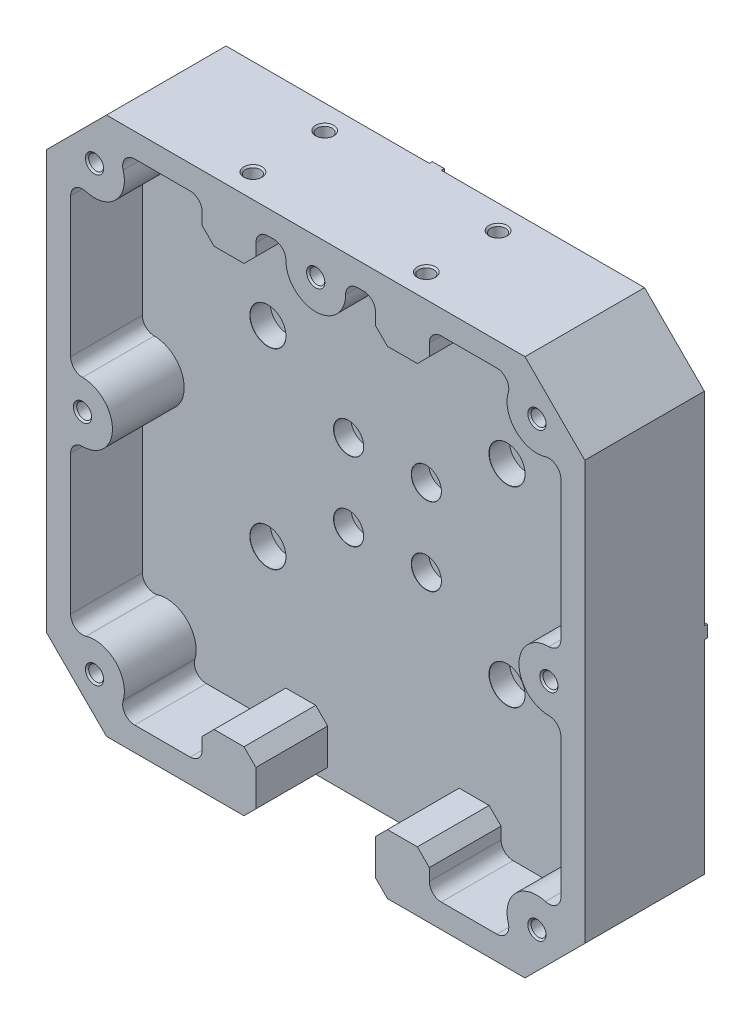
SolidWorks part; units mm, degrees
material "6061 Alloy"
ref_plane "Front Plane" through (0, 0, 0) normal (0, 0, 1) x (1, 0, 0)
ref_plane "Top Plane" through (0, 0, 0) normal (0, 1, 0) x (1, 0, 0)
ref_plane "Right Plane" through (0, 0, 0) normal (1, 0, 0) x (0, 0, -1)
sketch "Sketch1" plane through (0, 0, 0) normal (0, 0, 1) x (1, 0, 0)
  line L2 (-45, 45) -> (45, 45)
  line L3 (-45, 45) -> (-45, -45)
  line L4 (-45, -45) -> (45, -45)
  line L5 (45, 45) -> (45, -45)
  line L6 (-45, 45) -> (45, -45) construction
  line L7 (-45, -45) -> (45, 45) construction
  point P2 (0, 0)
  dimension "D2" = 90
  dimension "D3" = 90
extrude "Boss-Extrude1" add sketch "Sketch1" along normal blind 8
sketch "Z Axis Actuator Slot Position" plane through (0, 0, 8) normal (0, 0, 1) x (1, 0, 0)
  line L0 (-45, 0) -> (45, 0) construction
  line L1 (-45, 45) -> (-45, -45) construction
  line L2 (45, -45) -> (45, 45) construction
  line L3 (0, 45) -> (0, -45) construction
  line L4 (45, 45) -> (-45, 45) construction
  line L5 (-45, -45) -> (45, -45) construction
  point P0 (20, -16)
  point P3 (6.5, -6.5)
  point P17 (6.5, 6.5)
  point P18 (20, 16)
  point P19 (-20, 16)
  point P20 (-6.5, 6.5)
  point P21 (-6.5, -6.5)
  point P22 (-20, -16)
  dimension "D1" = 6.5
  dimension "D2" = 6.5
  dimension "D3" = 16
  dimension "D4" = 20
sketch "Sketch7" plane through (0, 0, 0) normal (0, 0, -1) x (-1, 0, 0)
  line L0 (-45, -45) -> (-45, 45) construction
  line L1 (45, -1) -> (-45, -1)
  line L2 (45, -1) -> (45, 1)
  line L3 (45, 1) -> (-45, 1)
  line L4 (-45, -1) -> (-45, 1)
  line L5 (45, -1) -> (-45, 1) construction
  line L6 (45, 1) -> (-45, -1) construction
  line L7 (45, 45) -> (45, -45) construction
  line L8 (0, 45) -> (0, -45) construction
  line L9 (-45, 45) -> (45, 45) construction
  line L10 (45, -45) -> (-45, -45) construction
  line L12 (1, -45) -> (-1, -45)
  line L13 (1, -45) -> (1, 45)
  line L14 (1, 45) -> (-1, 45)
  line L15 (-1, -45) -> (-1, 45)
  line L16 (1, -45) -> (-1, 45) construction
  line L17 (1, 45) -> (-1, -45) construction
  point P0 (0, 0)
  point P10 (0, 0)
  line M8 (-45, 45) -> (-45, -45)
  line M9 (-45, -45) -> (45, -45)
  line M10 (45, -45) -> (45, 45)
  line M11 (45, 45) -> (-45, 45)
  dimension "D1" = 2
  dimension "D2" = 2
extrude "Boss-Extrude2" add sketch "Sketch7" along normal blind 0.5 contours L1 L15 L3 M8 | L15 L1 L13 L3 | L15 L3 L13 M11 | L13 L1 L3 M10 | L15 L13 L1 M9
fillet "Fillet1" radius 0.5 4 edges at (1, -1, -0.25) (-1, -1, -0.25) (-1, 1, -0.25) (1, 1, -0.25)
sketch "Linear Rail Mounting Points" plane through (0, -45, 0) normal (0, -1, 0) x (-1, 0, 0)
  line L0 (-45, -8) -> (-45, 0) construction
  line L1 (-1, 0.5) -> (-1, 0) construction
  line L2 (-1, 0.5) -> (1, 0.5) construction
  point P0 (40, -11.5)
  point P1 (25, -11.5)
  point P3 (10, -11.5)
  point P5 (-5, -11.5)
  point P7 (-20, -11.5)
  point P9 (-35, -11.5)
  dimension "D1" = 10
  dimension "D2" = 11
  dimension "D3" = 26
  dimension "D4" = 41
  dimension "D5" = 4
  dimension "D6" = 19
  dimension "D7" = 12
ref_plane "Plane1" through (0, 0, 0) normal (0, -1, 0) x (-1, 0, 0)
sketch "Linear Actuator Mounting Positions" plane through (0, 0, 8) normal (0, 0, 1) x (1, 0, 0)
  line L0 (0, 45) -> (0, -45) construction
  line L1 (-45, 0) -> (45, 0) construction
  point P0 (42, -19.862)
  point P1 (42, 8.538)
  point P2 (1.5, 14.038)
  point P3 (1.5, -25.362)
  dimension "D1" = 40.5
  dimension "D2" = 5.5
  dimension "D3" = 28.4
  dimension "D4" = 5.5
  dimension "D5" = 1.5
  dimension "D6" = 25.362
sketch "Support Vertical Mounting Points" plane through (0, 0, 8) normal (0, 0, 1) x (1, 0, 0)
  line L0 (45, -45) -> (45, 45) construction
  line L3 (45, 45) -> (-45, 45) construction
  point P0 (40, 35)
  point P1 (10, 40)
  dimension "D1" = 5
  dimension "D2" = 10
  dimension "D3" = 30
  dimension "D4" = 5
sketch "Support Horizontal Mounting Points" plane through (45, 0, 0) normal (1, 0, 0) x (0, 0, -1)
  line L0 (-8, -45) -> (0, -45) construction
  line L1 (-8, -45) -> (-8, 45) construction
  line L2 (-8, 45) -> (0, 45) construction
  line L3 (0, 1) -> (0, 45) construction
  line L4 (0, -45) -> (0, -1) construction
  line L5 (-8, 0) -> (0.5, 0) construction
  line L6 (0.5, 1) -> (0.5, -1) construction
  point P0 (-3, -40)
  point P1 (-3, 40)
  point P6 (-5, -40)
  point P7 (-5, 40)
  point P14 (-5, 0)
  point P17 (-3, 0)
  dimension "D1" = 5
  dimension "D2" = 5
  dimension "D3" = 5
  dimension "D4" = 5
  dimension "D5" = 5
  dimension "D6" = 5
sketch "Sketch26" plane through (0, 0, 8) normal (0, 0, 1) x (1, 0, 0)
  line L0 (-45, 16) -> (-17, 0)
  line L1 (-17, 0) -> (-45, -16)
  line L3 (-45, -16) -> (-45, 16)
  line L4 (-45, 0) -> (45, 0) construction
  line L6 (-45, 45) -> (-45, -45) construction
  line L7 (45, -45) -> (45, 45) construction
  dimension "D1" = 28
  dimension "D2" = 32
extrude "Cut-Extrude1" [suppressed] cut sketch "Sketch26" against normal through all
fillet "Fillet2" [suppressed] radius 3
chamfer "Chamfer1" [suppressed] distance 1 angle 45
sketch "Sketch27" plane through (0, 0, 8) normal (0, 0, 1) x (1, 0, 0)
  line L4 (-40, 40) -> (-40, -40)
  line L6 (-40, 40) -> (-40, -40)
  line L7 (-40, -40) -> (40, -40)
  line L11 (-40, -40) -> (40, -40)
  line L13 (40, 40) -> (-40, 40)
  line L15 (40, 40) -> (-40, 40)
  line L16 (40, -40) -> (40, 40)
  line L23 (40, -40) -> (40, 40)
  circle A22 centre (-20, 16) radius 7.5
  circle A23 centre (-6.5, 6.5) radius 5
  circle A24 centre (1.5, 14.038) radius 4
  circle A25 centre (10, 40) radius 4
  circle A26 centre (6.5, 6.5) radius 5
  circle A27 centre (6.5, -6.5) radius 5
  circle A28 centre (-6.5, -6.5) radius 5
  circle A29 centre (-20, -16) radius 7.5
  circle A30 centre (20, -16) radius 7.5
  circle A31 centre (20, 16) radius 7.5
  circle A32 centre (1.5, -25.362) radius 4
  circle A33 centre (42, -19.862) radius 4
  circle A34 centre (42, 8.538) radius 4
  circle A35 centre (40, 35) radius 4
  dimension "D1" = 15
  dimension "D2" = 10
  dimension "D3" = 8
  dimension "D4" = 5
extrude "Cut-Extrude2" [suppressed] cut sketch "Sketch27" against normal blind 4.5
sketch "Sketch28" [suppressed] plane through (0, 0, 13.5) normal (0, 0, 1) x (1, 0, 0)
  line L0 (51.6428, -22.1747) -> (58.7052, -33.0775)
  line L1 (49.5685, -28.396) -> (55.3356, -35.2925)
  line L2 (44.0331, -27.8133) -> (35.4164, -34.5641)
  line L3 (33.5, -38.5) -> (33.5, -51.5)
  line L4 (38.5, -56.5) -> (51.5, -56.5)
  line L5 (56.5, -38.5) -> (56.5, -51.5)
  line L6 (72.5, -29) -> (72.5, -20)
  line L7 (18.5048, -25.25) -> (21.5359, -20)
  line L8 (85, -70) -> (85, -68.3261)
  line L11 (85, -32.9979) -> (85, -29)
  line L12 (85, -61.3979) -> (85, -39.9261)
  line L13 (85, -61.3979) -> (85, -39.9261)
  line L18 (85, -32.9979) -> (85, -29)
  line L22 (32.5, -29) -> (32.5, -20)
  line L23 (17.5048, -64.75) -> (20.5359, -70)
  line L24 (27.4641, -70) -> (30.4952, -64.75)
  line L25 (83.2679, -20) -> (81.5359, -23)
  line L27 (58.5048, -64.75) -> (61.5359, -70)
  line L28 (71.4952, -64.75) -> (68.4641, -70)
  line L29 (83.1363, -65.8973) -> (84.2356, -70)
  line L31 (85, -70) -> (85, -68.3261)
  line L39 (26.4186, -52.8142) -> (25.2131, -53.503)
  line L42 (85, -68.3261) -> (85, -70)
  line L57 (85, -70) -> (84.2356, -70)
  line L65 (26.4186, -52.8142) -> (25.2131, -53.503)
  line L66 (18.4329, -57.3774) -> (6, -64.4819)
  line L67 (18.4329, -57.3774) -> (6, -64.4819)
  line L68 (6, -64.4819) -> (6, -70)
  line L69 (6, -70) -> (42.5164, -70)
  line L73 (6, -70) -> (42.5164, -70)
  line L75 (50.4836, -70) -> (85, -70)
  line L77 (6, -64.4819) -> (6, -70)
  line L78 (50.4836, -70) -> (85, -70)
  line L79 (85, -21) -> (85, -20)
  line L80 (85, -21) -> (85, -20)
  line L81 (85, -20) -> (59, -20)
  line L82 (85, -20) -> (59, -20)
  line L83 (51, -20) -> (6, -20)
  line L84 (51, -20) -> (6, -20)
  line L85 (6, -20) -> (6, -25.5181)
  line L86 (6, -20) -> (6, -25.5181)
  line L87 (6, -25.5181) -> (18.4329, -32.6226)
  line L88 (6, -25.5181) -> (18.4329, -32.6226)
  line L89 (25.2131, -36.497) -> (26.4186, -37.1858)
  line L90 (25.2131, -36.497) -> (26.4186, -37.1858)
  circle A0 centre (55, -20) radius 4 construction
  circle A1 centre (65, -29) radius 7.5 construction
  circle A2 centre (46.5, -30.962) radius 4 construction
  circle A3 centre (51.5, -38.5) radius 5 construction
  circle A4 centre (38.5, -38.5) radius 5 construction
  circle A5 centre (38.5, -38.5) radius 5 construction
  circle A6 centre (38.5, -51.5) radius 5 construction
  circle A7 centre (38.5, -51.5) radius 5 construction
  circle A8 centre (51.5, -51.5) radius 5 construction
  circle A9 centre (51.5, -38.5) radius 5 construction
  arc A10 (85, -61.3979) -> (85, -68.3261) centre (87, -64.862) ccw
  arc A11 (85, -61.3979) -> (85, -68.3261) centre (87, -64.862) ccw
  arc A12 (50.4836, -70) -> (42.5164, -70) centre (46.5, -70.362) ccw
  arc A13 (85, -32.9979) -> (85, -39.9261) centre (87, -36.462) ccw
  arc A14 (85, -32.9979) -> (85, -39.9261) centre (87, -36.462) ccw
  circle A17 centre (65, -29) radius 7.5 construction
  arc A20 (50.4836, -70) -> (42.5164, -70) centre (46.5, -70.362) ccw
  circle A26 centre (51.5, -51.5) radius 5 construction
  circle A27 centre (46.5, -30.962) radius 4 construction
  circle A28 centre (65, -29) radius 7.5 construction
  circle A29 centre (65, -61) radius 7.5 construction
  circle A30 centre (65, -61) radius 7.5 construction
  arc A38 (85, -21) -> (85, -29) centre (85, -25) ccw
  arc A39 (85, -21) -> (85, -29) centre (85, -25) ccw
  arc A40 (51, -20) -> (59, -20) centre (55, -20) ccw
  arc A41 (51, -20) -> (59, -20) centre (55, -20) ccw
  arc A45 (26.4186, -52.8142) -> (26.4186, -37.1858) centre (21.9533, -45) ccw
  arc A46 (26.4186, -52.8142) -> (26.4186, -37.1858) centre (21.9533, -45) ccw
  arc A47 (18.4329, -57.3774) -> (25.2131, -53.503) centre (25, -61) ccw
  arc A48 (18.4329, -57.3774) -> (25.2131, -53.503) centre (25, -61) ccw
  arc A49 (25.2131, -36.497) -> (18.4329, -32.6226) centre (25, -29) ccw
  arc A50 (25.2131, -36.497) -> (18.4329, -32.6226) centre (25, -29) ccw
  dimension "D2" = 75
  dimension "D3" = 60
  dimension "D4" = 60
  dimension "D5" = 60
  dimension "D6" = 60
  dimension "D7" = 60
  dimension "D8" = 60
  dimension "D1" = 0
extrude "Boss-Extrude3" [suppressed] add sketch "Sketch28" along normal up to surface (4.5 mm away)
sketch "Sketch29" plane through (45, 0, 0) normal (1, 0, 0) x (0, 0, -1)
  line L1 (-5.5, -42.5) -> (-0.5, -42.5)
  line L2 (-5.5, -42.5) -> (-5.5, -37.5)
  line L3 (-5.5, -37.5) -> (-0.5, -37.5)
  line L4 (-0.5, -42.5) -> (-0.5, -37.5)
  line L5 (-5.5, -42.5) -> (-0.5, -37.5) construction
  line L6 (-5.5, -37.5) -> (-0.5, -42.5) construction
  line L7 (-5.5, -2.5) -> (-0.5, -2.5)
  line L8 (-5.5, -2.5) -> (-5.5, 2.5)
  line L9 (-5.5, 2.5) -> (-0.5, 2.5)
  line L10 (-0.5, -2.5) -> (-0.5, 2.5)
  line L11 (-5.5, -2.5) -> (-0.5, 2.5) construction
  line L12 (-5.5, 2.5) -> (-0.5, -2.5) construction
  line L13 (-5.5, 37.5) -> (-0.5, 37.5)
  line L14 (-5.5, 37.5) -> (-5.5, 42.5)
  line L15 (-5.5, 42.5) -> (-0.5, 42.5)
  line L16 (-0.5, 37.5) -> (-0.5, 42.5)
  line L17 (-5.5, 37.5) -> (-0.5, 42.5) construction
  line L18 (-5.5, 42.5) -> (-0.5, 37.5) construction
  point P0 (-3, -40)
  point P6 (-3, 0)
  point P12 (-3, 40)
  dimension "D1" = 5
extrude "Boss-Extrude4" [suppressed] add sketch "Sketch29" against normal blind 21
fillet "Fillet3" [suppressed] radius 2
fillet "Fillet4" [suppressed] radius 1
sketch "Sketch30" plane through (45, 0, 0) normal (1, 0, 0) x (0, 0, -1)
  line L8 (-3, -42) -> (-3, 42)
  line L10 (-3, -42) -> (-3, 42)
  line L20 (-5, 42) -> (-5, -42)
  line L21 (-5, -42) -> (-3, -42)
  line L23 (-3, 42) -> (-5, 42)
  line L24 (-5, 42) -> (-5, -42)
  line L25 (-5, -42) -> (-3, -42)
  line L27 (-3, 42) -> (-5, 42)
  circle A0 centre (-13, -20) radius 5
  circle A1 centre (-5, -20) radius 5
  circle A2 centre (-13, -45) radius 5
  circle A3 centre (-5, -45) radius 5
  circle A4 centre (-13, -70) radius 5
  circle A5 centre (-5, -70) radius 5
  dimension "D1" = 10
  dimension "D2" = 3
extrude "Cut-Extrude3" [suppressed] cut sketch "Sketch30" against normal blind 3
sketch "Sketch31" [suppressed] plane through (0, 0, 18) normal (0, 0, 1) x (1, 0, 0)
  line L0 (87, -64.862) -> (90, -64.862) construction
  line L1 (90, -75) -> (90, -15) construction
  line L2 (90, -68.862) -> (87, -68.862)
  line L3 (90, -68.862) -> (90, -60.862)
  line L4 (90, -60.862) -> (87, -60.862)
  line L5 (87, -68.862) -> (87, -60.862)
  line L8 (90, -32.462) -> (87, -32.462)
  line L9 (90, -32.462) -> (90, -40.462)
  line L10 (90, -40.462) -> (87, -40.462)
  line L11 (87, -32.462) -> (87, -40.462)
  line L12 (87, -36.462) -> (90, -36.462) construction
  line L13 (87, -40.4174) -> (87, -24.5826) construction
  dimension "D1" = 8
extrude "Boss-Extrude5" [suppressed] add sketch "Sketch31" against normal up to surface (15 mm away)
fillet "Fillet5" [suppressed] radius 2
sketch "Sketch32" [suppressed] plane through (87, 0, 0) normal (1, 0, 0) x (0, 0, -1)
  line L1 (-7.0993, -40.462) -> (-10.9007, -40.462)
  line L9 (-7.0993, -40.462) -> (-10.9007, -40.462)
  arc A2 (-9, -42) -> (-10.9007, -40.462) centre (-13, -45) ccw
  arc A3 (-7.0993, -40.462) -> (-9, -42) centre (-5, -45) ccw
  arc A4 (-9, -42) -> (-10.9007, -40.462) centre (-13, -45) ccw
  arc A5 (-7.0993, -40.462) -> (-9, -42) centre (-5, -45) ccw
  dimension "D1" = 0
extrude "Boss-Extrude6" [suppressed] add sketch "Sketch32" along normal up to surface (3 mm away)
hole_wizard "Tap Drill for M2 Tap1" [suppressed] positions "Sketch11" profile "Sketch12" hole size "M2" standard "GB"
sketch "Sketch11" plane through (0, -75, 0) normal (0, -1, 0) x (-1, 0, 0)
  line L0 (0, 0) -> (-44, 0) construction
  line L1 (0, -18) -> (0, 0) construction
  point P0 (-80, -9.5)
  point P3 (-65, -9.5)
  point P6 (-50, -9.5)
  point P9 (-35, -9.5)
  point P12 (-20, -9.5)
  point P15 (-5, -9.5)
  dimension "D1" = 9.5
  dimension "D2" = 5
  dimension "D3" = 20
  dimension "D4" = 35
  dimension "D5" = 50
  dimension "D6" = 65
  dimension "D7" = 80
sketch "Sketch12" plane through (80, -75, 9.5) normal (1, 0, 0) x (0, 0, -1)
  line L0 (0, 0) -> (0, 10.4807)
  line L1 (0, 10.4807) -> (0.8, 10)
  line L2 (0.8, 10) -> (0.8, 0.025)
  line L3 (0.8, 0.025) -> (0.825, 0)
  line L5 (0.825, 0) -> (0, 0)
  line L6 (-0.8, 0.025) -> (-0.825, 0) construction
  line L10 (0, 10.4807) -> (-0.8, 10) construction
  line L11 (0, -6.35) -> (0, 107.95) construction
  dimension "Hole Dia." = 1.6
  dimension "Hole Depth" = 10
  dimension "Near C'Sink Dia." = 1.65
  dimension "Near C'Sink Angle" = 90
  dimension "Drill Angle" = 118
mirror "Mirror1" [suppressed] about plane through (0, 0, 0) normal (0, -1, 0)
hole_wizard "CBORE for M2.5 Hexagon socket head cap screws1" positions "Sketch8" profile "Sketch9" counterbore size "M2.5" standard "GB" end condition through all
sketch "Sketch8" plane through (0, 0, 8) normal (0, 0, 1) x (1, 0, 0)
  point P0 (-6.5, 6.5)
  point P3 (6.5, 6.5)
  point P6 (-6.5, -6.5)
  point P9 (6.5, -6.5)
sketch "Sketch9" plane through (-6.5, 6.5, 8) normal (1, 0, 0) x (0, -1, 0)
  line L0 (0, 0) -> (0, 8.5)
  line L1 (0, 8.5) -> (1.35, 8.5)
  line L3 (1.35, 8.5) -> (1.35, 2.9)
  line L4 (2.5, 2.9) -> (1.35, 2.9)
  line L5 (2.5, 2.9) -> (2.5, 0.025)
  line L6 (2.5, 0.025) -> (2.525, 0)
  line L7 (2.525, 0) -> (0, 0)
  line L8 (-2.5, 0.025) -> (-2.525, 0) construction
  line L11 (0, -6.35) -> (0, 107.95) construction
  dimension "Thru Hole Dia." = 2.7
  dimension "Thru Hole Depth" = 8.5
  dimension "C'Bore Dia." = 5
  dimension "C'Bore Depth" = 2.9
  dimension "Near C'Sink Dia." = 5.05
  dimension "Near C'Sink Angle" = 90
hole_wizard "CBORE for M3 Hexagon socket head cap screws1" positions "Sketch4" profile "Sketch6" counterbore size "M3" standard "GB" end condition through all
sketch "Sketch4" plane through (0, 0, 8) normal (0, 0, 1) x (1, 0, 0)
  point P0 (20, -16)
  point P4 (20, 16)
  point P7 (-20, 16)
  point P10 (-20, -16)
sketch "Sketch6" plane through (20, -16, 8) normal (1, 0, 0) x (0, -1, 0)
  line L0 (0, 0) -> (0, 8.5)
  line L1 (0, 8.5) -> (1.6, 8.5)
  line L3 (1.6, 8.5) -> (1.6, 3.4)
  line L4 (3, 3.4) -> (1.6, 3.4)
  line L5 (3, 3.4) -> (3, 0.025)
  line L6 (3, 0.025) -> (3.025, 0)
  line L7 (3.025, 0) -> (0, 0)
  line L8 (-3, 0.025) -> (-3.025, 0) construction
  line L11 (0, -6.35) -> (0, 107.95) construction
  dimension "Thru Hole Dia." = 3.2
  dimension "Thru Hole Depth" = 8.5
  dimension "C'Bore Dia." = 6
  dimension "C'Bore Depth" = 3.4
  dimension "Near C'Sink Dia." = 6.05
  dimension "Near C'Sink Angle" = 90
other "Graphic1"
other "Graphic (Closed) -1"
other "Graphic (Closed) -2"
chamfer "Chamfer2" distance 10 angle 45 4 edges at (-45, 45, 4) (-45, -45, 4) (45, 45, 4) (45, -45, 4)
sketch "Sketch34" plane through (0, 0, 8) normal (0, 0, 1) x (1, 0, 0)
  line L8 (35, 45) -> (-35, 45)
  line L9 (-35, 45) -> (-45, 35)
  line L10 (-45, 35) -> (-45, -35)
  line L11 (-45, -35) -> (-35, -45)
  line L12 (-35, -45) -> (35, -45)
  line L13 (35, -45) -> (45, -35)
  line L14 (45, -35) -> (45, 35)
  line L15 (45, 35) -> (35, 45)
  line L16 (35, 45) -> (-35, 45)
  line L17 (-35, 45) -> (-45, 35)
  line L18 (-45, 35) -> (-45, -35)
  line L19 (-45, -35) -> (-35, -45)
  line L20 (-35, -45) -> (35, -45)
  line L21 (35, -45) -> (45, -35)
  line L22 (45, -35) -> (45, 35)
  line L23 (45, 35) -> (35, 45)
  line L32 (33.3431, 41) -> (-33.3431, 41)
  line L33 (-33.3431, 41) -> (-41, 33.3431)
  line L34 (-41, 33.3431) -> (-41, -33.3431)
  line L35 (-41, -33.3431) -> (-33.3431, -41)
  line L36 (-33.3431, -41) -> (33.3431, -41)
  line L37 (33.3431, -41) -> (41, -33.3431)
  line L38 (41, -33.3431) -> (41, 33.3431)
  line L39 (41, 33.3431) -> (33.3431, 41)
  line L40 (33.3431, 41) -> (-33.3431, 41)
  line L41 (-33.3431, 41) -> (-41, 33.3431)
  line L42 (-41, 33.3431) -> (-41, -33.3431)
  line L43 (-41, -33.3431) -> (-33.3431, -41)
  line L44 (-33.3431, -41) -> (33.3431, -41)
  line L45 (33.3431, -41) -> (41, -33.3431)
  line L46 (41, -33.3431) -> (41, 33.3431)
  line L47 (41, 33.3431) -> (33.3431, 41)
  dimension "D1" = 0
  dimension "D2" = 4
extrude "Boss-Extrude8" add sketch "Sketch34" along normal blind 12
sketch "Sketch35" plane through (0, 0, 20) normal (0, 0, 1) x (1, 0, 0)
  line L1 (35, 45) -> (-35, 45) construction
  line L2 (-45, 35) -> (-45, -35) construction
  line L3 (0, 45) -> (0, -45) construction
  line L4 (0, 45) -> (0, -45) construction
  line L5 (-45, 0) -> (45, 0) construction
  point P0 (-37, 37)
  point P3 (37, 37)
  point P8 (0, 39)
  point P12 (37, -37)
  point P17 (-37, -37)
  point P18 (-39, 0)
  point P19 (39, 0)
  dimension "D1" = 8
  dimension "D2" = 8
  dimension "D3" = 6
  dimension "D4" = 6
sketch "Sketch36" plane through (0, 0, 8) normal (0, 0, 1) x (1, 0, 0)
  line L8 (45, 35) -> (35, 45)
  line L9 (35, 45) -> (-35, 45)
  line L10 (-35, 45) -> (-45, 35)
  line L11 (-45, 35) -> (-45, -35)
  line L12 (-45, -35) -> (-35, -45)
  line L13 (-35, -45) -> (35, -45)
  line L14 (35, -45) -> (45, -35)
  line L15 (45, -35) -> (45, 35)
  line L16 (45, 35) -> (35, 45)
  line L17 (35, 45) -> (-35, 45)
  line L18 (-35, 45) -> (-45, 35)
  line L19 (-45, 35) -> (-45, -35)
  line L20 (-45, -35) -> (-35, -45)
  line L21 (-35, -45) -> (35, -45)
  line L22 (35, -45) -> (45, -35)
  line L23 (45, -35) -> (45, 35)
  circle A0 centre (-37, 37) radius 5
  circle A1 centre (0, 39) radius 5
  circle A2 centre (37, 37) radius 5
  circle A3 centre (39, 0) radius 5
  circle A4 centre (-39, 0) radius 5
  circle A5 centre (-37, -37) radius 5
  circle A6 centre (37, -37) radius 5
  line M9 (41, 33.3431) -> (33.3431, 41)
  line M10 (33.3431, 41) -> (-33.3431, 41)
  line M11 (-33.3431, 41) -> (-41, 33.3431)
  line M12 (-41, 33.3431) -> (-41, -33.3431)
  line M13 (-41, -33.3431) -> (-33.3431, -41)
  line M15 (33.3431, -41) -> (41, -33.3431)
  line M16 (41, -33.3431) -> (41, 33.3431)
  dimension "D1" = 10
  dimension "D2" = 0
extrude "Boss-Extrude9" add sketch "Sketch36" along normal up to surface (12 mm away) contours A0 M11 | A1 M10 | A2 M9 | A3 M16 | A4 M12 | A5 M13 | A6 M15 up to face at (0, 0, 20)
sketch "Sketch37" plane through (0, 0, 20) normal (0, 0, 1) x (1, 0, 0)
  line L0 (-33.3431, -41) -> (33.3431, -41) construction
  line L1 (10, -45) -> (-10, -45)
  line L2 (10, -45) -> (10, -37)
  line L3 (10, -37) -> (-10, -37)
  line L4 (-10, -45) -> (-10, -37)
  line L5 (10, -45) -> (-10, -37) construction
  line L6 (10, -37) -> (-10, -45) construction
  line L7 (-35, -45) -> (35, -45) construction
  point P0 (0, -41)
  dimension "D1" = 20
extrude "Cut-Extrude4" cut sketch "Sketch37" against normal up to surface (12 mm away) up to face at (0, 3.4091, 8)
sketch "Sketch41" plane through (0, 0, 8) normal (0, 0, 1) x (1, 0, 0)
  line L1 (-19, 41) -> (-10, 41)
  line L2 (-19, 41) -> (-19, 35)
  line L3 (-19, 35) -> (-10, 35)
  line L4 (-10, 41) -> (-10, 35)
  line L5 (0, 45) -> (0, -45) construction
  line L6 (35, 45) -> (-35, 45) construction
  line L7 (10, -45) -> (-10, -45) construction
  line L8 (-45, 0) -> (45, 0) construction
  line L9 (-45, 35) -> (-45, -35) construction
  line L10 (45, -35) -> (45, 35) construction
  line L11 (-10, -41) -> (-10, -35)
  line L12 (-19, -35) -> (-10, -35)
  line L13 (-19, -41) -> (-19, -35)
  line L14 (-19, -41) -> (-10, -41)
  line L15 (-10, -45) -> (-10, -41) construction
  line L16 (19, -41) -> (10, -41)
  line L17 (19, -41) -> (19, -35)
  line L18 (19, -35) -> (10, -35)
  line L19 (10, -41) -> (10, -35)
  line L20 (10, 41) -> (10, 35)
  line L21 (19, 35) -> (10, 35)
  line L22 (19, 41) -> (19, 35)
  line L23 (19, 41) -> (10, 41)
  line L24 (-4.5826, 41) -> (-33.3431, 41) construction
  dimension "D1" = 9
  dimension "D2" = 6
extrude "Boss-Extrude10" add sketch "Sketch41" along normal up to surface (12 mm away) up to face at (0, -2.8529, 20)
chamfer "Chamfer3" distance 2 angle 45 10 edges at (10, -45, 14) (-10, -45, 14) (-19, 35, 14) (-10, 35, 14) (19, 35, 14) (10, 35, 14) (19, -35, 14) (10, -35, 14) (-19, -35, 14) (-10, -35, 14)
fillet "Fillet6" radius 2 4 edges at (-33.3431, -41, 14) (-33.4917, -40.8515, 8) (-33.4917, -40.8515, 20) (-33.6402, -40.7029, 14)
fillet "Fillet7" radius 2 4 edges at (-40.8515, -33.4917, 8) (-41, -33.3431, 14) (-40.8515, -33.4917, 20) (-40.7029, -33.6402, 14)
fillet "Fillet8" radius 2 4 edges at (-41, 33.3431, 14) (-40.8515, 33.4917, 8) (-40.8515, 33.4917, 20) (-40.7029, 33.6402, 14)
fillet "Fillet9" radius 2 4 edges at (-33.4917, 40.8515, 8) (-33.3431, 41, 14) (-33.4917, 40.8515, 20) (-33.6402, 40.7029, 14)
fillet "Fillet10" radius 2 4 edges at (33.3431, 41, 14) (33.4917, 40.8515, 8) (33.4917, 40.8515, 20) (33.6402, 40.7029, 14)
fillet "Fillet11" radius 2 4 edges at (40.8515, 33.4917, 8) (40.8515, 33.4917, 20) (41, 33.3431, 14) (40.7029, 33.6402, 14)
fillet "Fillet12" radius 2 4 edges at (41, -33.3431, 14) (40.8515, -33.4917, 8) (40.8515, -33.4917, 20) (40.7029, -33.6402, 14)
fillet "Fillet13" radius 2 4 edges at (33.4917, -40.8515, 8) (33.3431, -41, 14) (33.4917, -40.8515, 20) (33.6402, -40.7029, 14)
hole_wizard "M3 Tapped Hole2" positions "Sketch38" profile "Sketch39" tap size "M3" standard "GB" end condition through all
sketch "Sketch38" plane through (0, 0, 20) normal (0, 0, 1) x (1, 0, 0)
  point P0 (-37, 37)
  point P3 (0, 39)
  point P6 (37, 37)
  point P9 (-39, 0)
  point P12 (39, 0)
  point P15 (-37, -37)
  point P18 (37, -37)
sketch "Sketch39" plane through (-37, 37, 20) normal (1, 0, 0) x (0, -1, 0)
  line L0 (0, 0) -> (0, 20.5)
  line L1 (0, 20.5) -> (1.25, 20.5)
  line L2 (1.25, 20.5) -> (1.25, 0.275)
  line L3 (1.25, 0.275) -> (1.525, 0)
  line L5 (1.525, 0) -> (0, 0)
  line L6 (-1.25, 0.275) -> (-1.525, 0) construction
  line L11 (0, -6.35) -> (0, 107.95) construction
  dimension "Thru Tap Drill Dia." = 2.5
  dimension "Thru Tap Drill Depth" = 20.5
  dimension "Near C'Sink Dia." = 3.05
  dimension "Near C'Sink Angle" = 90
fillet "Fillet14" radius 2 12 edges at (-41, -4.5826, 14) (-41, 4.5826, 14) (-4.5826, 41, 14) (4.5826, 41, 14) (41, 4.5826, 14) (41, -4.5826, 14) (-19, -41, 14) (19, -41, 14) (19, 41, 14) (-19, 41, 14) (10, 41, 14) (-10, 41, 14)
sketch "Sketch42" plane through (0, -45, 0) normal (0, -1, 0) x (1, 0, 0)
  line L0 (-45, 20) -> (45, 20) construction
  line L1 (-45, 10) -> (45, 10) construction
  line L2 (-45, 0) -> (-45, 20) construction
  line L3 (45, 20) -> (45, 0) construction
  line L4 (0, -0.5) -> (0, 20) construction
  line L5 (1, -0.5) -> (-1, -0.5) construction
  line L6 (-12, 8) -> (-12, 20) construction
  point P0 (-14.5, 16)
  point P15 (14.5, 16)
  point P17 (14.5, 4)
  point P18 (-14.5, 4)
  dimension "D1" = 4
  dimension "D2" = 2.5
hole_wizard "M3 Tapped Hole1" positions "Sketch43" profile "Sketch44" tap size "M3" standard "GB"
sketch "Sketch43" plane through (0, -45, 0) normal (0, -1, 0) x (-1, 0, 0)
  point P0 (-14.5, -4)
  point P3 (-14.5, -16)
  point P6 (14.5, -4)
  point P9 (14.5, -16)
sketch "Sketch44" plane through (14.5, -45, 4) normal (1, 0, 0) x (0, 0, -1)
  line L0 (0, 0) -> (0, 8.7511)
  line L1 (0, 8.7511) -> (1.25, 8)
  line L2 (1.25, 8) -> (1.25, 0.275)
  line L3 (1.25, 0.275) -> (1.525, 0)
  line L5 (1.525, 0) -> (0, 0)
  line L6 (-1.25, 0.275) -> (-1.525, 0) construction
  line L10 (0, 8.7511) -> (-1.25, 8) construction
  line L11 (0, -6.35) -> (0, 107.95) construction
  dimension "Tap Drill Dia." = 2.5
  dimension "Tap Drill Depth" = 8
  dimension "Near C'Sink Dia." = 3.05
  dimension "Near C'Sink Angle" = 90
  dimension "Drill Angle" = 118
ref_plane "Plane3" through (0, 0, 0) normal (0, 1, 0) x (1, 0, 0)
mirror "Mirror2" about plane through (0, 0, 0) normal (0, 1, 0) of "M3 Tapped Hole1"
